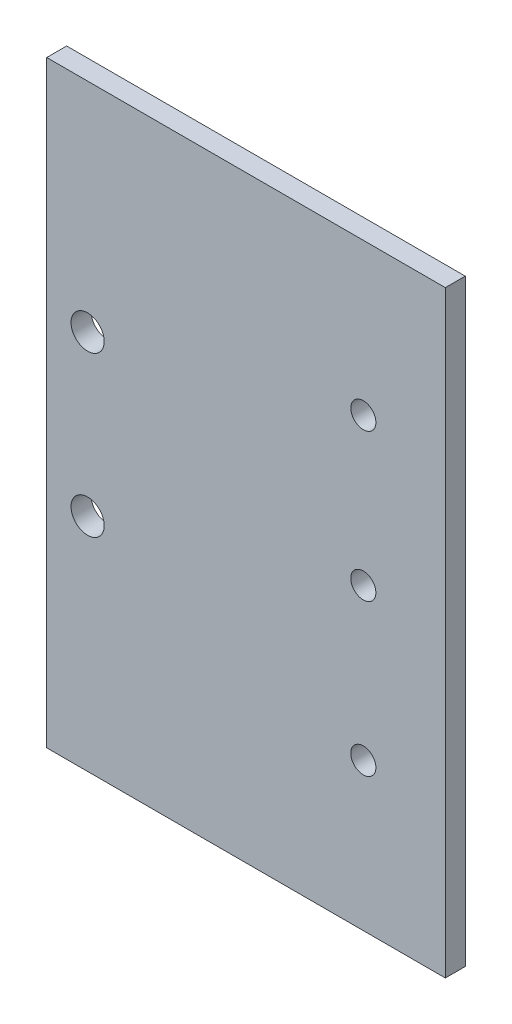
SolidWorks part; units mm, degrees
ref_plane "Front Plane" through (0, 0, 0) normal (0, 0, 1) x (1, 0, 0)
ref_plane "Top Plane" through (0, 0, 0) normal (0, 1, 0) x (1, 0, 0)
ref_plane "Right Plane" through (0, 0, 0) normal (1, 0, 0) x (0, 0, -1)
sketch "Sketch2" plane through (0, 0, 0) normal (0, 0, 1) x (1, 0, 0)
  line L0 (-123.0109, -74.4947) -> (-143.5848, -74.4947) construction
  line L1 (-123.0109, 0.5053) -> (-223.0109, 0.5053)
  line L2 (-123.0109, 0.5053) -> (-123.0109, -149.4947)
  line L3 (-123.0109, -149.4947) -> (-223.0109, -149.4947)
  line L4 (-223.0109, 0.5053) -> (-223.0109, -149.4947)
  line L5 (-143.5848, -74.4947) -> (-143.5848, -112.5) construction
  line L6 (-143.5848, -112.5) -> (-143.5848, -37.5) construction
  line L7 (-212.756, -54.0129) -> (-223.0109, -54.0129) construction
  line L8 (-212.756, -94.0129) -> (-223.0109, -94.0129) construction
  circle A0 centre (-143.5848, -37.5) radius 3.15
  circle A1 centre (-143.5848, -112.5) radius 3.15
  circle A2 centre (-143.5848, -74.4947) radius 3.15
  circle A3 centre (-212.756, -54.0129) radius 4.165
  circle A4 centre (-212.756, -94.0129) radius 4.165
  dimension "D1" = 100
  dimension "D2" = 150
extrude "Boss-Extrude1" add sketch "Sketch2" along normal blind 5 contours L4 L3 L2 L1
sketch "Sketch3" plane through (0, 0, 0) normal (0, 0, -1) x (-1, 0, 0)
  circle A0 centre (143.5848, -37.5) radius 3.15
  circle A1 centre (143.5848, -74.4947) radius 3.15
  circle A2 centre (143.5848, -112.5) radius 3.15
  circle A3 centre (212.756, -54.0129) radius 4.165
  circle A4 centre (212.756, -94.0129) radius 4.165
extrude "Cut-Extrude1" cut sketch "Sketch3" against normal blind 5
